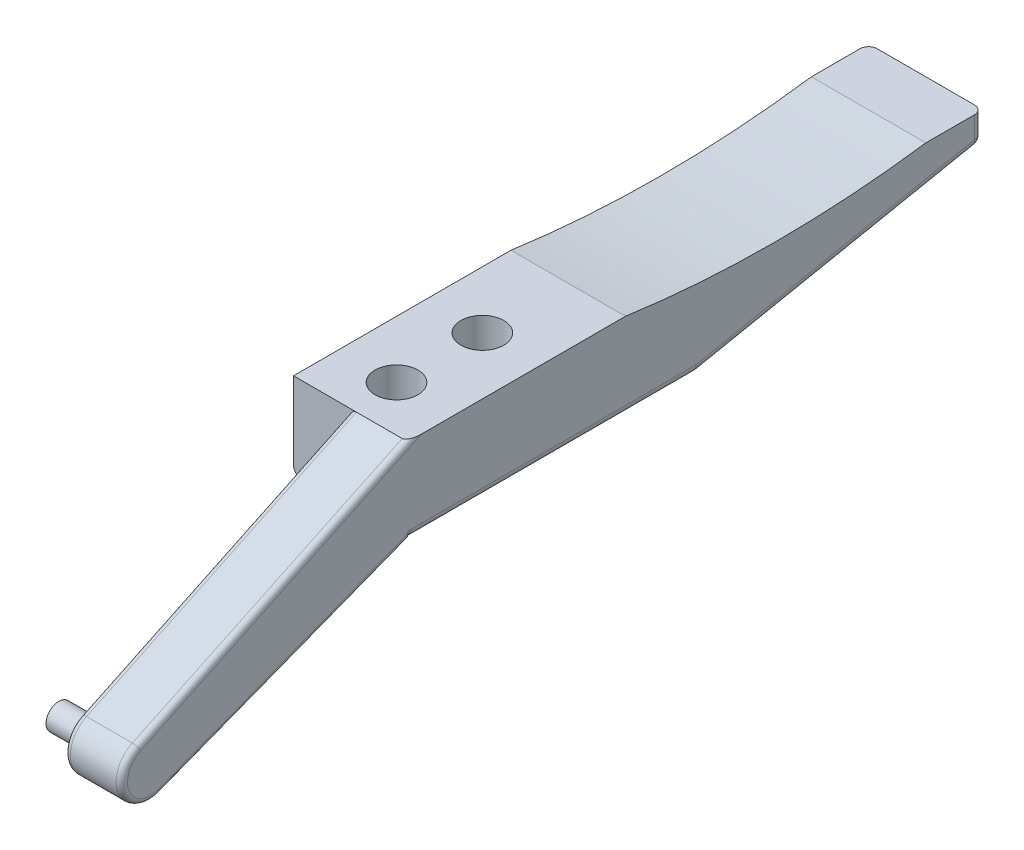
SolidWorks part; units mm, degrees
ref_plane "Front Plane" through (0, 0, 0) normal (0, 0, 1) x (1, 0, 0)
ref_plane "Top Plane" through (0, 0, 0) normal (0, 1, 0) x (1, 0, 0)
ref_plane "Right Plane" through (0, 0, 0) normal (1, 0, 0) x (0, 0, -1)
sketch "Sketch1" plane through (0, 0, 0) normal (0, 1, 0) x (1, 0, 0)
  line L1 (-20, 75) -> (20, 75)
  line L3 (-20, -75) -> (20, -75)
  line L4 (20, -75) -> (20, 75)
  line L5 (-20, -75) -> (-20, 75)
  circle A0 centre (0, -61.1649) radius 7.5
  circle A1 centre (0, -31.1649) radius 7.5
extrude "Boss-Extrude1" add sketch "Sketch1" against normal blind 30 contours L5 L1 L4 L3
sketch "Sketch3" plane through (0, 0, 0) normal (0, 1, 0) x (1, 0, 0)
  circle A0 centre (0, -60) radius 7.5
  circle A1 centre (0, -30) radius 7.5
extrude "Cut-Extrude1" cut sketch "Sketch3" against normal blind 30 contours A0 | A1
sketch "Sketch4" plane through (-20, 0, 0) normal (-1, 0, 0) x (0, 0, 1)
  line L1 (-75, -30) -> (-75, 0) construction
  line L2 (-75, -8) -> (0, -30)
  line L3 (75, -30) -> (-75, -30) construction
  line L4 (0, -30) -> (-75, -30)
  line L5 (-75, -30) -> (-75, -8)
extrude "Cut-Extrude2" cut sketch "Sketch4" against normal blind 49
sketch "Sketch6" plane through (0, 0, -75) normal (0, 0, -1) x (-1, 0, 0)
  line L1 (-20, 0) -> (20, 0)
  line L2 (-20, 0) -> (-20, -30)
  line L3 (-20, -30) -> (20, -30)
  line L4 (20, 0) -> (20, -30)
extrude "Boss-Extrude2" add sketch "Sketch6" along normal blind 50 and the other way blind 87
sketch "Sketch7" plane through (-20, 0, 0) normal (-1, 0, 0) x (0, 0, 1)
  line L1 (-125, -30) -> (-125, 0) construction
  line L2 (-125, -10) -> (-25, -30)
  line L3 (75, -30) -> (-125, -30) construction
  line L4 (-25, -30) -> (-125, -30)
  line L5 (-125, -30) -> (-125, -10)
extrude "Cut-Extrude3" cut sketch "Sketch7" against normal blind 50
sketch "Sketch8" plane through (0, 0, 75) normal (0, 0, 1) x (1, 0, 0)
  line L10 (20, -30) -> (6, -30)
  line L11 (-20, -30) -> (20, -30) construction
  line L12 (6, -30) -> (6, 0)
  line L13 (-20, 0) -> (20, 0) construction
  line L14 (6, 0) -> (20, 0)
  line L15 (20, 0) -> (20, -30)
  line L16 (-20, -30) -> (-6, -30)
  line L17 (-6, -30) -> (-6, 0)
  line L18 (-6, 0) -> (-20, 0)
  line L19 (-20, -30) -> (-20, 0) construction
  line L20 (-20, 0) -> (-20, -30)
extrude "Boss-Extrude4" add sketch "Sketch8" along normal blind 50
sketch "Sketch11" plane through (0, 0, 0) normal (0, 1, 0) x (1, 0, 0)
  line L0 (6, -75) -> (20, -75)
  line L1 (20, -125) -> (20, 125) construction
  line L2 (20, -75) -> (20, -125)
  line L3 (20, -125) -> (6, -125)
  line L4 (6, -125) -> (6, -75)
  line L5 (-6, -75) -> (-6, -125)
  line L6 (-6, -125) -> (-20, -125)
  line L7 (-20, -125) -> (-20, -75)
  line L8 (-20, -125) -> (-20, 125) construction
  line L9 (-20, -75) -> (-6, -75)
extrude "Cut-Extrude4" cut sketch "Sketch11" against normal blind 15
sketch "Sketch12" plane through (0, 0, 125) normal (0, 0, 1) x (1, 0, 0)
  line L1 (-20, -15) -> (-6, -15)
  line L2 (-20, -15) -> (-20, -30)
  line L3 (-20, -30) -> (-6, -30)
  line L4 (-6, -15) -> (-6, -30)
  line L5 (6, -15) -> (20, -15)
  line L6 (6, -15) -> (6, -30)
  line L7 (6, -30) -> (20, -30)
  line L8 (20, -15) -> (20, -30)
extrude "Boss-Extrude5" add sketch "Sketch12" along normal blind 10
sketch "Sketch13" plane through (-6, 0, 0) normal (1, 0, 0) x (0, 0, -1)
  circle A0 centre (-125, -22.5) radius 5
extrude "Boss-Extrude6" add sketch "Sketch13" along normal up to surface (12 mm away) contours A0 up to face at (6, -22.5, 105)
sketch "Sketch14" plane through (0, -30, 0) normal (0, -1, 0) x (1, 0, 0)
  circle A0 centre (0, 60) radius 7.5
  circle A1 centre (0, 60) radius 6
  circle A2 centre (0, 30) radius 6
  circle A3 centre (0, 30) radius 7.5
extrude "Boss-Extrude7" add sketch "Sketch14" against normal blind 5
sketch "Sketch15" plane through (20, 0, 0) normal (1, 0, 0) x (0, 0, -1)
  line L0 (125, 0) -> (105, 0)
  line L1 (-75, 0) -> (125, 0) construction
  circle A0 centre (52.5, 373.9316) radius 377.5991
extrude "Cut-Extrude5" cut sketch "Sketch15" against normal blind 50 contours A0
fillet "Fillet1" radius 3 2 edges at (20, -30, 55) (-20, -30, 55)
fillet "Fillet2" radius 3 8 edges at (-20, -18.5, -82.5) (-19.1213, -29.1213, -29.3934) (0, -30, -25) (19.1213, -29.1213, -29.3934) (-20, -5, -125) (20, -5, -125) (0, -10, -125) (20, -18.5, -82.5)
sketch "Sketch17" plane through (0, 0, 75) normal (0, 0, 1) x (1, 0, 0)
  line L0 (20, 0) -> (20, -30)
  line L1 (14.0365, -30) -> (20, -30)
  line L2 (6, -30) -> (17, -30) construction
  line L3 (20, 0) -> (-20, 0)
  line L4 (-20, 0) -> (-20, -30)
  line L5 (-20, -30) -> (14.0365, -30)
extrude "Boss-Extrude11" add sketch "Sketch17" along normal up to surface (60 mm away) up to face at (13.9243, -23.5243, 135)
sketch "Sketch23" plane through (0, 0, 135) normal (0, 0, 1) x (1, 0, 0)
  line L0 (-20, -15) -> (0, -15)
  line L1 (-20, 0) -> (-20, -30) construction
  line L3 (0, -30) -> (0, -15)
  line L4 (-20, -30) -> (20, -30) construction
  line L6 (-20, -30) -> (0, -30)
  line L7 (-20, -15) -> (-20, -30)
  line L9 (-20, -30) -> (20, -30)
  line L10 (-20, -30) -> (-20, 0)
  line L11 (-20, 0) -> (20, 0)
  line L12 (20, -30) -> (20, 0)
  line M1 (-20, 0) -> (-20, -30)
  line M2 (-20, -30) -> (20, -30)
  line M3 (20, -30) -> (20, 0)
  line M4 (20, 0) -> (-20, 0)
extrude "Cut-Extrude8" cut sketch "Sketch23" against normal up to surface (60 mm away) contours L3 L0 M2 M3 M4 M1 region at (3.3333, -12.5, 135) up to face at (19.2071, -29.2071, 75)
sketch "Sketch25" plane through (0, 0, 75) normal (0, 0, 1) x (1, 0, 0)
  line L0 (-20, -15) -> (-20, 0)
  line L1 (-20, 0) -> (0, 0)
  line L2 (-20, 0) -> (20, 0) construction
  line L3 (0, 0) -> (0, -15)
  line L4 (0, -15) -> (-20, -15)
extrude "Boss-Extrude13" add sketch "Sketch25" along normal up to surface (60 mm away) up to face at (-10, -22.5, 135)
sketch "Sketch26" plane through (0, 0, 0) normal (1, 0, 0) x (0, 0, -1)
  circle A0 centre (-125, -15) radius 5
extrude "Boss-Extrude14" add sketch "Sketch26" along normal up to surface (20 mm away) up to face at (20, -9.3154, -31.9576)
sketch "Sketch27" plane through (0, 0, 75) normal (0, 0, 1) x (1, 0, 0)
  line L1 (20, 0) -> (-20, 0)
  line L2 (20, 0) -> (20, -60)
  line L3 (20, -60) -> (-20, -60)
  line L4 (-20, 0) -> (-20, -60)
extrude "Boss-Extrude15" add sketch "Sketch27" along normal up to surface (60 mm away) up to face at (-10, -15, 135)
sketch "Sketch28" plane through (0, 0, 75) normal (0, 0, -1) x (-1, 0, 0)
  line L0 (20, -27) -> (20, -60) construction
  line L1 (-20, -60) -> (20, -60)
  line L2 (-20, -60) -> (-20, -30)
  line L3 (-20, -30) -> (20, -30)
  line L4 (20, -60) -> (20, -30)
extrude "Cut-Extrude9" cut sketch "Sketch28" against normal blind 1
sketch "Sketch29" plane through (0, 0, 135) normal (0, 0, 1) x (1, 0, 0)
  line L0 (20, 0) -> (-20, 0) construction
  line L1 (20, -60) -> (0, -60)
  line L2 (20, -60) -> (20, 0)
  line L3 (20, 0) -> (0, 0)
  line L4 (0, -60) -> (0, 0)
extrude "Cut-Extrude10" cut sketch "Sketch29" against normal up to surface (59 mm away) up to face at (0, -45, 76)
fillet "Fillet6" radius 3 1 edges at (-20, -30, 75.5)
fillet "Fillet7" radius 3 1 edges at (20, -30, 75.5)
sketch "Sketch30" plane through (0, 0, 135) normal (0, 0, 1) x (1, 0, 0)
  line L0 (-20, 0) -> (-20, -30)
  line L1 (-20, 0) -> (-20, -60) construction
  line L2 (-20, -15) -> (0, -15)
  line L3 (0, 0) -> (0, -60) construction
  line L4 (0, -15) -> (0, 0)
  line L5 (0, 0) -> (-20, 0)
  line M1 (0, -60) -> (0, 0)
  line M2 (0, 0) -> (-20, 0)
  line M3 (-20, 0) -> (-20, -60)
extrude "Cut-Extrude11" cut sketch "Sketch30" against normal up to surface (59 mm away) contours L2 M3 M1 M2 region at (-10, -7.5, 135) up to face at (11.5243, -17.5243, 76)
sketch "Sketch31" plane through (0, 0, 0) normal (1, 0, 0) x (0, 0, -1)
  line L0 (-129.7694, -41.2162) -> (-129.0122, -40.847)
  line L1 (-76, -15) -> (-76, -30)
  line L2 (-76, -30) -> (-118.7075, -57.7744)
  line L3 (-129.6113, -41.0081) -> (-129.7694, -41.2162)
  line L4 (-89.6197, -15) -> (-129.6113, -41.0081)
  line L5 (-76, -30) -> (-76, -60)
  line L6 (-76, -60) -> (-135, -60)
  line L7 (-135, -60) -> (-135, -15)
  line L8 (-135, -15) -> (-76, -15)
  line L9 (-96, -19.1494) -> (-129.6113, -41.0081) construction
  line L10 (-96, -15) -> (-96, -19.1494) construction
  circle A0 centre (-125.0122, -50.0122) radius 10
  line M9 (-76, -15) -> (-135, -15)
  line M10 (-135, -15) -> (-135, -60)
  line M11 (-135, -60) -> (-76, -60)
  line M12 (-76, -60) -> (-76, -30)
  dimension "D1" = 20
extrude "Cut-Extrude13" cut sketch "Sketch31" against normal blind 28 contours A0 M10 M11 | A0 L2 M11 M12 | A0 L3 L4 M9 M10 region at (0, -24.9817, 119.9741) region at (0, -57.7806, 132.7806) region at (0, -50.0084, 91.4032)
sketch "Sketch32" plane through (0, 0, 0) normal (1, 0, 0) x (0, 0, -1)
  line L0 (-76, -30) -> (-76, 0)
  line L1 (-76, 0) -> (-129.7694, -41.2162)
  line L2 (-129.7694, -41.2162) -> (-76, -30)
extrude "Boss-Extrude16" add sketch "Sketch32" against normal up to surface (20 mm away) up to face at (-20, -28.5466, 55.3206)
sketch "Sketch33" plane through (0, 0, 0) normal (1, 0, 0) x (0, 0, -1)
  circle A0 centre (-125.0122, -50.0122) radius 5
extrude "Boss-Extrude17" add sketch "Sketch33" along normal up to surface (20 mm away) contours A0 up to face at (20, -11.526, -18.3379)
ref_plane "Plane2" through (0, 10, 0) normal (0, 1, 0) x (1, 0, 0)
sketch "Sketch34" plane through (0, 0, 0) normal (1, 0, 0) x (0, 0, -1)
  line L0 (-129.6113, -41.0081) -> (-129.7694, -41.2162)
  line L1 (-129.6113, -41.0081) -> (-76, 0)
  line L2 (-76, 0) -> (-76, -30)
  line L3 (-76, -30) -> (-76, 0) construction
  line L4 (-76, -30) -> (-118.7075, -57.7744)
  arc A0 (-129.7694, -41.2162) -> (-118.7075, -57.7744) centre (-125.0122, -50.0122) ccw
extrude "Cut-Extrude15" cut sketch "Sketch34" against normal up to surface (20 mm away) up to face at (-20, -30.8448, 56.4126)
extrude "Cut-Extrude16" cut sketch "Sketch34<2>" along normal up to surface (20 mm away) up to face at (20, -11.526, -18.3379)
sketch "Sketch34<2>" plane through (0, 0, 0) normal (1, 0, 0) x (0, 0, -1) same geometry as "Sketch34"
extrude "Boss-Extrude19" add sketch "Sketch34<3>" along normal up to surface (20 mm away) up to face at (20, -11.526, -18.3379)
sketch "Sketch34<3>" plane through (0, 0, 0) normal (1, 0, 0) x (0, 0, -1) same geometry as "Sketch34"
sketch "Sketch38" plane through (0, 0, 0) normal (-1, 0, 0) x (0, 0, 1)
  circle A0 centre (125.0122, -50.0122) radius 5
sketch "Sketch39" plane through (0, 0, 0) normal (-1, 0, 0) x (0, 0, 1)
  line L0 (162.0273, -59.1835) -> (76, -78.9424)
  line L1 (169.997, -40.8408) -> (76, 0)
  line L2 (76, -30) -> (76, 0) construction
  line L3 (76, 0) -> (129.6113, -41.0081) construction
  line L4 (76, 0) -> (76, -30)
  line L6 (162.0273, -59.1835) -> (76, -30)
  line L7 (76, -78.9424) -> (76, -30)
  arc A0 (162.0273, -59.1835) -> (169.997, -40.8408) centre (166.0122, -50.0122) ccw
  line M6 (129.6113, -41.0081) -> (76, 0)
  line M8 (76, -30) -> (118.7075, -57.7744)
  arc M9 (118.7075, -57.7744) -> (129.7694, -41.2162) centre (125.0122, -50.0122) ccw
  line M10 (129.7694, -41.2162) -> (129.6113, -41.0081)
extrude "Cut-Extrude17" cut sketch "Sketch39" against normal blind 23 contours L7 L0 L6 M9 M8 | L6 M9 M8 region at (0, -58.461, 102.3812) region at (0, -47.5284, 112.7515)
extrude "Boss-Extrude21" add sketch "Sketch39<3>" against normal blind 20 contours L6 A0 L1 M6 M10 M9 region at (0, -36.3816, 138.4753)
sketch "Sketch39<3>" plane through (0, 0, 0) normal (-1, 0, 0) x (0, 0, 1) same geometry as "Sketch39"
sketch "Sketch40" plane through (0, -4.0074, 0) normal (-1, 0, 0) x (0, 0, 1)
  circle A0 centre (166.0122, -50.0122) radius 4.5
extrude "Boss-Extrude22" add sketch "Sketch40" along normal up to surface (12 mm away)
ref_plane "Plane5" through (0, 0, 0) normal (-1, 0, 0) x (0, 0, 1)
sketch "Sketch42" plane through (0, 0, 0) normal (-1, 0, 0) x (0, 0, 1)
  line L0 (166.0122, -54.0196) -> (166.0122, -54.0122)
  line L1 (170.3172, -44.9863) -> (76, 0)
  line L2 (76, 0) -> (76, -30)
  line L3 (162.4124, -63.3418) -> (76, -30)
  line L4 (175.8593, -55.7544) -> (179.2704, -36.4741)
  line L5 (179.2704, -36.4741) -> (76, 0)
  circle A0 centre (166.0122, -54.0122) radius 10
extrude "Cut-Extrude18" cut sketch "Sketch42" against normal blind 20 contours A0 L4 L5 L1 region at (0, -28.5967, 144.6768)
extrude "Boss-Extrude23" add sketch "Sketch42<4>" against normal blind 20 contours A0 L1 L2 L3 | A0 region at (0, -31.8969, 115.5317) region at (0, -48.8269, 174.2302)
sketch "Sketch42<4>" plane through (0, 0, 0) normal (-1, 0, 0) x (0, 0, 1) same geometry as "Sketch42"
sketch "Sketch43" plane through (0, 0, 0) normal (-1, 0, 0) x (0, 0, 1)
  circle A0 centre (166.0122, -54.0196) radius 5.5
extrude "Boss-Extrude24" add sketch "Sketch43" along normal blind 2
fillet "Fillet8" radius 2 6 edges at (20, -46.6709, 119.2062) (20, -57.9675, 175.1967) (0, -46.6709, 119.2062) (0, -57.9675, 175.1967) (20, -22.4932, 123.1586) (0, -22.4932, 123.1586)
